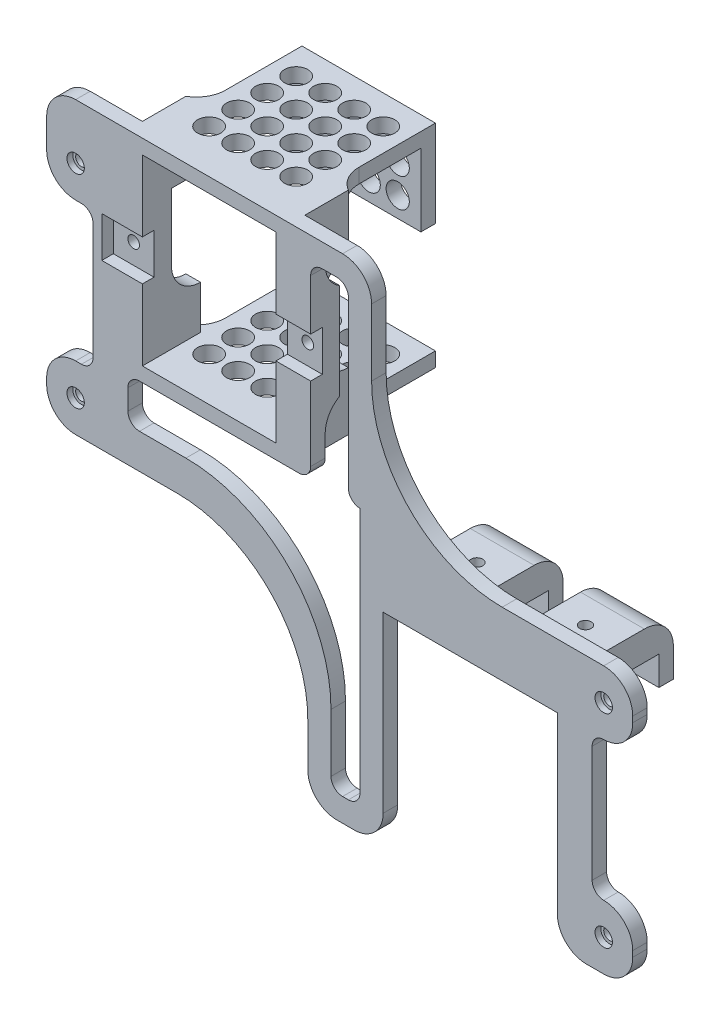
SolidWorks part; units mm, degrees
ref_plane "Přední rovina" through (0, 0, 0) normal (0, 0, 1) x (1, 0, 0)
ref_plane "Horní rovina" through (0, 0, 0) normal (0, 1, 0) x (1, 0, 0)
ref_plane "Pravá rovina" through (0, 0, 0) normal (1, 0, 0) x (0, 0, -1)
sketch "Skica1" plane through (0, 0, 0) normal (0, 0, 1) x (1, 0, 0)
  line L0 (0, 0) -> (101, 0) construction
  line L1 (0, 0) -> (0, 101) construction
  line L2 (-101, 101) -> (101, 101)
  line L3 (101, 101) -> (101, -101)
  line L4 (-101, 101) -> (-101, -101)
  line L5 (-101, -101) -> (101, -101)
  point P8 (-101, 0)
  dimension "D1" = 202
  dimension "D2" = 202
extrude "Přidat vysunutím1" add sketch "Skica1" along normal blind 5
sketch "Skica2" plane through (0, 0, 5) normal (0, 0, 1) x (1, 0, 0)
  line L0 (101, -101) -> (101, 101) construction
  line L1 (101, 101) -> (-101, 101) construction
  line L2 (11, 56) -> (11, 101)
  line L3 (56, 11) -> (101, 11)
  line L4 (11, 101) -> (101, 101)
  line L5 (101, 101) -> (101, 11)
  line L6 (0, 0) -> (-101, 101) construction
  line L7 (-56, -11) -> (-101, -11)
  line L8 (-101, -11) -> (-101, -101)
  line L9 (-101, -101) -> (-11, -101)
  line L10 (-11, -56) -> (-11, -101)
  arc A0 (11, 56) -> (56, 11) centre (56, 56) ccw
  arc A1 (-56, -11) -> (-11, -56) centre (-56, -56) cw
  dimension "D1" = 90
extrude "Odebrat vysunutím1" cut sketch "Skica2" against normal blind 10
sketch "Skica3" plane through (0, 0, 5) normal (0, 0, 1) x (1, 0, 0)
  line L0 (0, 0) -> (91, 0) construction
  line L1 (0, 0) -> (0, 101) construction
  line L2 (11, 101) -> (-101, 101) construction
  circle A2 centre (91, 0) radius 2
  circle A3 centre (-91, 0) radius 2
  circle A4 centre (91, -70) radius 2
  circle A5 centre (-91, 70) radius 2
  dimension "D4" = 70
  dimension "D5" = 2
  dimension "D3" = 4
  dimension "D1" = 2
  dimension "D2" = 91
  dimension "D6" = 70
extrude "Odebrat vysunutím2" cut sketch "Skica3" against normal through all
sketch "Skica4" plane through (0, 0, 5) normal (0, 0, 1) x (1, 0, 0)
  line L0 (0, 0) -> (91, 0) construction
  line L1 (0, 0) -> (0, 95) construction
  circle A2 centre (91, 0) radius 3
  circle A3 centre (-91, 0) radius 3
  circle A4 centre (91, -70) radius 3
  circle A5 centre (-91, 70) radius 3
  dimension "D4" = 70
  dimension "D5" = 2
  dimension "D3" = 6
  dimension "D1" = 2
  dimension "D2" = 91
  dimension "D6" = 70
extrude "Odebrat vysunutím4" cut sketch "Skica4" along direction (0, 0, 1) on the side against the normal blind 2
sketch "Skica6" plane through (0, 0, 5) normal (0, 0, 1) x (1, 0, 0)
  line L0 (75, -11) -> (15, -11)
  line L1 (-11, -101) -> (101, -101) construction
  line L2 (15, -11) -> (15, -101)
  line L3 (75, -11) -> (75, -101)
  line L4 (45, -101) -> (45, 12.3652) construction
  line L5 (75, -101) -> (15, -101)
  arc A0 (11, 56) -> (56, 11) centre (56, 56) ccw construction
  point P12 (45, -11)
  dimension "D1" = 60
  dimension "D2" = 90
extrude "Odebrat vysunutím5" cut sketch "Skica6" against normal blind 10
sketch "Skica7" plane through (0, 0, 0) normal (0, 0, -1) x (-1, 0, 0)
  line L0 (-75, -11) -> (-75, -1)
  line L2 (-15, -11) -> (-15, -1)
  line L3 (-15, -1) -> (-75, -1)
  line L4 (-75, -11) -> (-15, -11)
  dimension "D1" = 10
extrude "Přidat vysunutím2" add sketch "Skica7" along normal blind 35
sketch "Skica8" plane through (0, -11, 0) normal (0, -1, 0) x (1, 0, 0)
  line L0 (15, -35) -> (15, -30)
  line L1 (15, -35) -> (15, 0) construction
  line L2 (15, -30) -> (75, -30)
  line L3 (75, -35) -> (75, 0) construction
  line L4 (75, -30) -> (75, -35)
  line L5 (75, -35) -> (15, -35)
  dimension "D1" = 5
extrude "Přidat vysunutím3" add sketch "Skica8" along normal blind 10
sketch "Skica9" plane through (0, -11, 0) normal (0, -1, 0) x (1, 0, 0)
  line L0 (45, -30) -> (45, -16) construction
  line L1 (75, -30) -> (15, -30) construction
  line L2 (45, -16) -> (26.3, -16) construction
  circle A0 centre (26.3, -16) radius 2
  circle A1 centre (63.7, -16) radius 2
  dimension "D2" = 4
  dimension "D1" = 18.7
  dimension "D3" = 14
extrude "Odebrat vysunutím6" cut sketch "Skica9" against normal blind 10
fillet "Zaoblit1" radius 8 2 edges at (15, -6, 0) (45, -1, 0)
sketch "Skica11" plane through (0, 0, 5) normal (0, 0, 1) x (1, 0, 0)
  line L0 (-45, 101) -> (-45, 21) construction
  line L1 (11, 101) -> (-101, 101) construction
  line L2 (-68, 21) -> (-22, 21)
  line L3 (-22, 21) -> (-22, 84)
  line L4 (-22, 84) -> (-68, 84)
  line L5 (-68, 21) -> (-68, 84)
  point P8 (-45, 84)
  dimension "D1" = 63
  dimension "D2" = 46
  dimension "D3" = 17
extrude "Odebrat vysunutím8" cut sketch "Skica11" against normal blind 10
sketch "Skica13" plane through (0, 0, 5) normal (0, 0, 1) x (1, 0, 0)
  line L0 (-68, 52.5) -> (-22, 52.5) construction
  line L1 (-68, 84) -> (-68, 21) construction
  line L2 (-22, 21) -> (-22, 84) construction
  line L3 (-45, 52.5) -> (-45, 84) construction
  line L4 (-22, 84) -> (-68, 84) construction
  line L5 (-68, 45.5) -> (-82, 45.5)
  line L6 (-82, 45.5) -> (-82, 59.5)
  line L7 (-68, 52.5) -> (-82, 52.5) construction
  line L8 (-68, 59.5) -> (-82, 59.5)
  line L9 (-68, 45.5) -> (-68, 59.5)
  line L10 (-22, 59.5) -> (-8, 59.5)
  line L11 (-8, 45.5) -> (-8, 59.5)
  line L12 (-22, 45.5) -> (-8, 45.5)
  line L13 (-22, 45.5) -> (-22, 59.5)
  dimension "D1" = 14
  dimension "D2" = 14
sketch "Skica19" plane through (0, 0, 0) normal (0, 0, -1) x (-1, 0, 0)
  line L0 (68, 52.5) -> (101, 52.5) construction
  line L1 (68, 84) -> (68, 21) construction
  line L2 (101, 101) -> (101, -11) construction
  line L3 (45, 84) -> (45, 54.4833) construction
  line L4 (22, 84) -> (68, 84) construction
  line L5 (80, 36) -> (80, 69)
  line L6 (80, 69) -> (68, 69)
  line L7 (68, 69) -> (68, 36)
  line L8 (80, 36) -> (68, 36)
  line L9 (10, 69) -> (22, 69)
  line L10 (10, 36) -> (10, 69)
  line L11 (10, 36) -> (22, 36)
  line L12 (22, 69) -> (22, 36)
  point P15 (80, 52.5)
  dimension "D1" = 12
  dimension "D2" = 15
extrude "Přidat vysunutím7" add sketch "Skica19" along normal blind 5
extrude "Odebrat vysunutím9" cut sketch "Skica13" against normal blind 4
sketch "Skica14" plane through (0, 0, 1) normal (0, 0, 1) x (1, 0, 0)
  line L0 (-68, 52.5) -> (-75, 52.5) construction
  line L1 (-68, 45.5) -> (-68, 59.5) construction
  line L2 (-45, 84) -> (-45, 21) construction
  line L3 (-22, 84) -> (-68, 84) construction
  line L4 (-68, 21) -> (-22, 21) construction
  circle A0 centre (-75, 52.5) radius 2
  circle A1 centre (-15, 52.5) radius 2
  dimension "D2" = 4
  dimension "D1" = 7
extrude "Odebrat vysunutím10" cut sketch "Skica14" against normal blind 5
sketch "Skica15" plane through (0, 0, 0) normal (0, 0, -1) x (-1, 0, 0)
  line L0 (22, 84) -> (22, 89)
  line L1 (22, 89) -> (68, 89)
  line L2 (68, 89) -> (68, 84)
  line L3 (22, 84) -> (68, 84) construction
  line L4 (68, 84) -> (22, 84)
  line L5 (10, 52.5) -> (80, 52.5) construction
  line L12 (10, 69) -> (10, 36) construction
  line L13 (80, 36) -> (80, 69) construction
  line L14 (68, 16) -> (68, 21)
  line L15 (22, 16) -> (68, 16)
  line L16 (22, 21) -> (22, 16)
  line L17 (68, 21) -> (22, 21)
  dimension "D1" = 5
extrude "Přidat vysunutím4" add sketch "Skica15" along normal blind 50
sketch "Skica16" plane through (0, 84, 0) normal (0, -1, 0) x (1, 0, 0)
  line L6 (-22, -50) -> (-68, -50) construction
  line L7 (-68, -50) -> (-22, -50)
  line L8 (-68, -50) -> (-68, -45)
  line L9 (-68, -45) -> (-22, -45)
  line L10 (-22, -50) -> (-22, -45)
  line L11 (-68, -50) -> (-68, 0) construction
  line L12 (-22, -50) -> (-22, 0) construction
  dimension "D1" = 5
extrude "Přidat vysunutím5" add sketch "Skica16" along normal blind 25
sketch "Skica17" plane through (0, 0, 0) normal (0, 0, -1) x (-1, 0, 0)
  line L5 (73, 16) -> (73, 36)
  line L7 (22, 89) -> (17, 89)
  line L8 (17, 89) -> (17, 69)
  line L9 (17, 69) -> (22, 69)
  line L10 (22, 69) -> (22, 89)
  line L11 (45, 78.5) -> (45, 101) construction
  line L12 (-11, 101) -> (101, 101) construction
  line L13 (73, 69) -> (68, 69)
  line L14 (73, 89) -> (73, 69)
  line L15 (68, 89) -> (73, 89)
  line L16 (68, 69) -> (68, 89)
  line L25 (10, 52.5) -> (80, 52.5) construction
  line L26 (10, 69) -> (10, 36) construction
  line L27 (80, 36) -> (80, 69) construction
  line L29 (68, 16) -> (73, 16)
  line L30 (68, 36) -> (68, 16)
  line L31 (73, 36) -> (68, 36)
  line L32 (17, 36) -> (22, 36)
  line L33 (17, 16) -> (17, 36)
  line L34 (22, 16) -> (17, 16)
  line L35 (22, 36) -> (22, 16)
  dimension "D1" = 20
  dimension "D2" = 5
extrude "Přidat vysunutím6" add sketch "Skica17" along normal blind 15
fillet "Zaoblit2" radius 10 11 edges at (-22, 86.5, -15) (-68, 86.5, -15) (-13.5, 69, 0) (-13.5, 36, 0) (-76.5, 69, 0) (-76.5, 36, 0) (-70.5, 36, -5) (-68, 18.5, -15) (-22, 18.5, -15) (-19.5, 36, -5) (-19.5, 69, -5)
sketch "Skica21" plane through (0, 0, 5) normal (0, 0, 1) x (1, 0, 0)
  line L0 (101, -101) -> (101, 11) construction
  line L1 (-11, -101) -> (101, -101)
  line L2 (-11, -101) -> (-11, -81)
  line L3 (-11, -81) -> (101, -81)
  line L4 (101, -101) -> (101, -81)
  line L5 (11, 101) -> (11, 56) construction
  line L6 (-101, 101) -> (11, 101)
  line L7 (-101, 101) -> (-101, 89)
  line L8 (-101, 89) -> (11, 89)
  line L9 (11, 101) -> (11, 89)
  line L10 (-73, 89) -> (-17, 89) construction
  dimension "D1" = 12
  dimension "D2" = 20
extrude "Odebrat vysunutím15" cut sketch "Skica21" against normal through all
sketch "Skica22" plane through (0, 0, 5) normal (0, 0, 1) x (1, 0, 0)
  line L0 (101, -81) -> (101, 11) construction
  line L1 (101, -59) -> (87, -59)
  line L2 (101, -59) -> (101, -11)
  line L3 (101, -11) -> (87, -11)
  line L4 (87, -59) -> (87, -11)
  line L5 (-101, 89) -> (-101, -11) construction
  line L6 (-101, 59) -> (-85, 59)
  line L7 (-101, 59) -> (-101, 11)
  line L8 (-101, 11) -> (-85, 11)
  line L9 (-85, 59) -> (-85, 11)
  circle A0 centre (-91, 70) radius 2 construction
  circle A1 centre (-91, 0) radius 2 construction
  circle A2 centre (91, 0) radius 3 construction
  circle A3 centre (91, -70) radius 2 construction
  dimension "D3" = 11
  dimension "D5" = 11
  dimension "D6" = 11
  dimension "D1" = 16
  dimension "D2" = 11
  dimension "D4" = 14
extrude "Odebrat vysunutím16" cut sketch "Skica22" against normal through all
sketch "Skica23" plane through (0, 0, 0) normal (0, 0, -1) x (-1, 0, 0)
  line L0 (-7, 7) -> (-7, -11) construction
  line L1 (73, 16) -> (10, 16)
  line L2 (73, 16) -> (73, 1)
  line L3 (73, 1) -> (53, 1)
  line L4 (-7, 16) -> (-7, -28.5)
  line L5 (-7, -73) -> (3, -73)
  line L7 (3, -73) -> (3, -49)
  line L9 (-7, -73) -> (-7, -28.5)
  line L12 (11, -81) -> (11, -56) construction
  line L13 (-15, -81) -> (11, -81) construction
  line L14 (-3, 81) -> (-3, 16)
  line L16 (10, 16) -> (10, 81)
  line L17 (10, 81) -> (-3, 81)
  line L18 (17, 89) -> (-11, 89) construction
  line L19 (-11, 89) -> (-11, 56) construction
  line L20 (10, 77.6603) -> (10, 27.3397) construction
  line L21 (-3, 16) -> (-7, 16)
  arc A0 (3, -49) -> (53, 1) centre (53, -49) cw
  point P20 (0, 0)
  point P23 (-3, 48.5)
  point P26 (9.4781, 81)
  dimension "D4" = 50
  dimension "D1" = 15
  dimension "D2" = 8
  dimension "D3" = 8
  dimension "D5" = 8
  dimension "D6" = 8
extrude "Odebrat vysunutím17" cut sketch "Skica23" against normal through all
sketch "Skica24" plane through (0, -1, 0) normal (0, 1, 0) x (1, 0, 0)
  line L0 (15, 8) -> (75, 8) construction
  line L1 (37, 8) -> (53, 8)
  line L2 (37, 8) -> (37, 35)
  line L3 (37, 35) -> (53, 35)
  line L4 (53, 8) -> (53, 35)
  line L5 (15, 35) -> (75, 35) construction
  line L6 (75, 35) -> (75, 8) construction
  line L7 (15, 35) -> (15, 8) construction
  point P12 (15, 21.5)
  dimension "D1" = 22
  dimension "D2" = 22
extrude "Odebrat vysunutím18" cut sketch "Skica24" against normal through all both and the other way through all
fillet "Zaoblit3" radius 10 14 edges at (101, 11, 2.5) (-101, -11, 2.5) (11, 89, 2.5) (-101, 89, 2.5) (15, -81, 2.5) (-11, -81, 2.5) (75, -81, 2.5) (101, -81, 2.5) (101, -59, 2.5) (101, -11, 2.5) (-101, 11, 2.5) (-101, 59, 2.5) (64, -1, -35) (26, -1, -35)
fillet "Zaoblit4" radius 4 12 edges at (87, -59, 2.5) (87, -11, 2.5) (-85, 11, 2.5) (-85, 59, 2.5) (3, 81, 2.5) (-10, 81, 2.5) (3, 16, 2.5) (-10, 16, 2.5) (-73, 16, 2.5) (-73, 1, 2.5) (7, -73, 2.5) (-3, -73, 2.5)
sketch "Skica25" plane through (0, 16, 0) normal (0, -1, 0) x (1, 0, 0)
  line L0 (-60, -50) -> (-60, -10) construction
  line L1 (-22, -50) -> (-68, -50) construction
  line L2 (-68, -50) -> (-68, -23.6603) construction
  line L3 (-60, -10) -> (-30, -10) construction
  circle A0 centre (-60, -10) radius 4
  circle A1 centre (-50, -10) radius 4
  circle A2 centre (-40, -10) radius 4
  circle A3 centre (-30, -10) radius 4
  circle A4 centre (-50, -20) radius 4
  circle A5 centre (-40, -20) radius 4
  circle A6 centre (-30, -20) radius 4
  circle A7 centre (-50, -30) radius 4
  circle A8 centre (-40, -30) radius 4
  circle A9 centre (-30, -30) radius 4
  circle A10 centre (-50, -40) radius 4
  circle A11 centre (-40, -40) radius 4
  circle A12 centre (-30, -40) radius 4
  circle A13 centre (-60, -20) radius 4
  circle A14 centre (-60, -30) radius 4
  circle A15 centre (-60, -40) radius 4
  dimension "D1" = 8
  dimension "D3" = 4
  dimension "D5" = 10
  dimension "D6" = 10
  dimension "D7" = 10
  dimension "D8" = 40
  dimension "D2" = 8
  dimension "D4" = 4
extrude "Odebrat vysunutím19" cut sketch "Skica25" against normal through all both and the other way through all
sketch "Skica26" plane through (0, 0, -45) normal (0, 0, 1) x (1, 0, 0)
  line L0 (-60, 76) -> (-60, 59) construction
  line L1 (-22, 59) -> (-68, 59) construction
  line L2 (-60, 76) -> (-22, 76) construction
  line L3 (-22, 59) -> (-22, 84) construction
  line L4 (-68, 84) -> (-68, 59.5) construction
  line L5 (-60, 66) -> (-60, 76) construction
  line L6 (-22, 84) -> (-68, 84) construction
  line L7 (-50, 66) -> (-50, 76) construction
  circle A0 centre (-60, 76) radius 4
  circle A1 centre (-50, 76) radius 4
  circle A2 centre (-40, 76) radius 4
  circle A3 centre (-30, 76) radius 4
  circle A4 centre (-50, 66) radius 4
  circle A5 centre (-40, 66) radius 4
  circle A6 centre (-30, 66) radius 4
  circle A7 centre (-60, 66) radius 4
  dimension "D1" = 8
  dimension "D4" = 4
  dimension "D6" = 10
  dimension "D7" = 10
  dimension "D2" = 8
  dimension "D3" = 8
  dimension "D5" = 2
extrude "Odebrat vysunutím20" cut sketch "Skica26" against normal through all both and the other way through all
